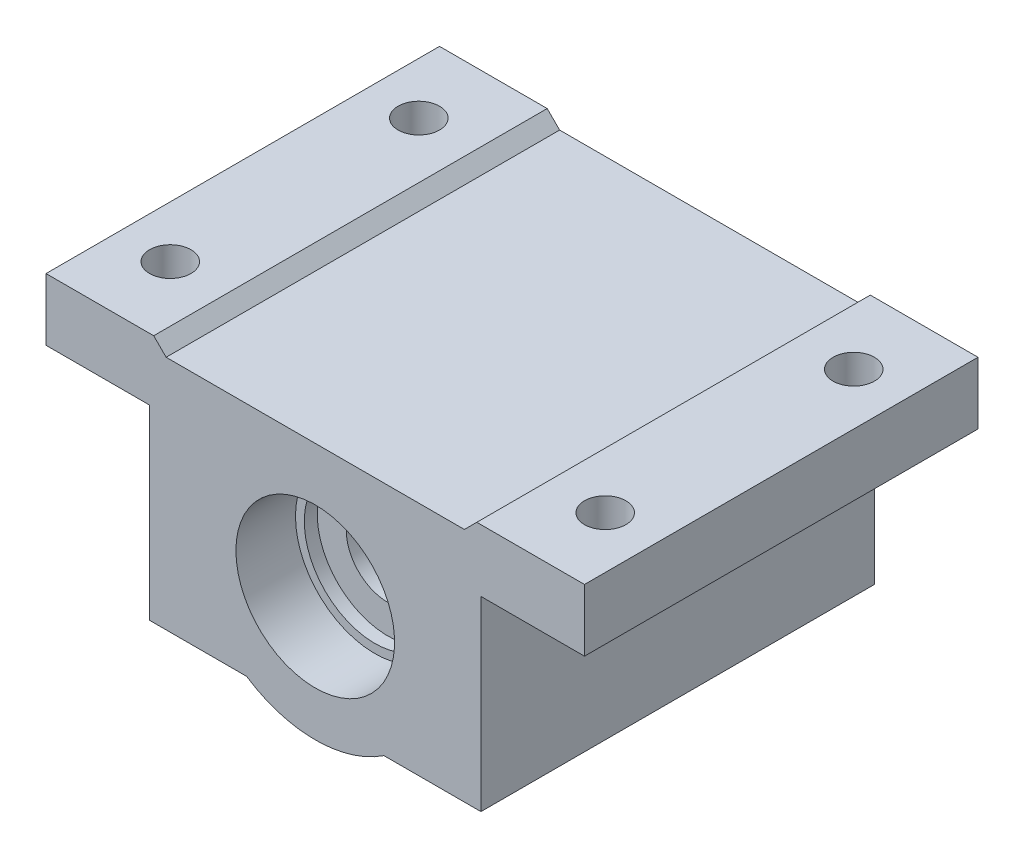
SolidWorks part; units mm, degrees
note: The reader was unsure of these and kept them because the rebuilt part matched: shared geometry of "Grooves<2>".
other "Pillow Block" parameters "D1"=31.4478, "For Shaft Dia"=6.35, "D2"=12.6007, "Supplier Grv Dia P"=13.5128, "Ht G"=11.1125, "Flange Thick H"=4.7625, "Overall Wd D"=41.275, "Overall Ht F"=20.6375, "Supplier Wd G"=25.4, "D3"=16.7204, "D4"=1.4178, "D5"=41.275, "D6"=12.2773, "D7"=50.8, "Supplier Body Height K"=19.05, "Overall Lg B"=30.1625, "Supplier Overall Wd S"=119.0625, "Outside to Outside Grooves"=228.6, "Supplier Grv Wd O"=0.9906, "Dia L"=3.175, "Mounting Holes Center-to-Center J"=33.3375, "Mounting Holes Center-to-Center K"=19.05, "Supplier F"=19.05
material "6063-O, Extruded Rod (SS)"
ref_plane "Front" through (0, 0, 0) normal (0, 0, 1) x (1, 0, 0)
ref_plane "Top" through (0, 0, 0) normal (0, 1, 0) x (1, 0, 0)
ref_plane "Right" through (0, 0, 0) normal (1, 0, 0) x (0, 0, -1)
sketch "Sketch1" plane through (0, 0, 0) normal (0, 0, 1) x (1, 0, 0)
  line L0 (-12.7, -9.525) -> (-12.7, 6.35) construction
  line L1 (-12.7, -9.525) -> (12.7, -9.525) construction
  line L2 (-12.7, 6.35) -> (-20.6375, 6.35)
  line L3 (-20.6375, 11.1125) -> (20.6375, 11.1125) construction
  line L4 (-20.6375, 6.35) -> (-20.6375, 11.1125)
  line L5 (12.7, -9.525) -> (12.7, 6.35) construction
  line L6 (12.7, 6.35) -> (20.6375, 6.35)
  line L7 (20.6375, 6.35) -> (20.6375, 11.1125)
  line L8 (0, 11.1125) -> (0, -9.525) construction
  line L9 (5.2651, -7.9375) -> (12.7, -7.9375)
  line L10 (-12.7, 6.35) -> (-12.7, -7.9375)
  line L11 (-12.7, -7.9375) -> (-5.2651, -7.9375)
  line L12 (12.7, -7.9375) -> (12.7, 6.35)
  line L13 (-12.3825, 11.1125) -> (12.3825, 11.1125) construction
  line L14 (-12.3825, 11.1125) -> (-11.43, 10.16)
  line L15 (-11.43, 10.16) -> (11.43, 10.16)
  line L16 (11.43, 10.16) -> (12.3825, 11.1125)
  line L17 (-12.3825, 11.1125) -> (-20.6375, 11.1125)
  line L18 (12.3825, 11.1125) -> (20.6375, 11.1125)
  circle A0 centre (0, 0) radius 3.175 construction
  circle A1 centre (0, 0) radius 6.0808
  circle A2 centre (0, 0) radius 9.525 construction
  arc A3 (-5.2651, -7.9375) -> (5.2651, -7.9375) centre (0, 0) ccw
  circle A4 centre (0, 0) radius 6.7564 construction
  dimension "D2" = 12.1615
  dimension "D4" = 45
  dimension "D3" = 45
  dimension "D6" = 8.255
  dimension "D1" = 0.9525
extrude "Main Body" add sketch "Sketch1" along normal mid plane 30.1625
sketch "Sketch3" plane through (0, 11.1125, 0) normal (0, 1, 0) x (1, 0, 0)
  line L1 (-16.6687, -9.525) -> (16.6687, -9.525) construction
  line L2 (-16.6687, -9.525) -> (-16.6687, 9.525) construction
  line L3 (-16.6687, 9.525) -> (16.6687, 9.525) construction
  line L4 (16.6687, -9.525) -> (16.6687, 9.525) construction
  line L5 (-12.3825, 15.0813) -> (-20.6375, 15.0813) construction
  line L6 (-16.6687, 9.525) -> (16.6687, -9.525) construction
  line L7 (-16.6687, 9.525) -> (-16.6687, -9.525) construction
  circle A0 centre (-16.6687, 9.525) radius 1.5875
  circle A1 centre (16.6687, 9.525) radius 1.5875
  circle A2 centre (16.6687, -9.525) radius 1.5875
  circle A3 centre (-16.6687, -9.525) radius 1.5875
  point P5 (0, 0)
  dimension "D1" = 5.5562
extrude "Mounting Holes" cut sketch "Sketch3" against normal up to surface (4.7625 mm away) up to face at (16.6688, 6.35, 0)
ref_plane "Plane1" through (0, 0, 0) normal (0, 0, 1) x (1, 0, 0)
sketch "Sketch8" plane through (0, 0, 0) normal (0, 0, 1) x (1, 0, 0)
  circle A0 centre (0, 0) radius 6.0808 construction
  circle A1 centre (0, 0) radius 6.0808
  circle A2 centre (0, 0) radius 3.175 construction
  circle A3 centre (0, 0) radius 3.175
extrude "Interior" add sketch "Sketch8" along normal mid plane 19.05 separate body
sketch "Grooves" plane through (0, 0, 0) normal (1, 0, 0) x (0, 0, -1)
  line L1 (9.525, -6.7564) -> (9.525, 6.7564) construction
  line L2 (9.525, -3.175) -> (9.525, 3.175) construction
  line L4 (-9.525, 3.175) -> (-9.525, -3.175) construction
  line L5 (9.525, -5.4051) -> (9.525, -6.7564)
  line L6 (9.525, -6.7564) -> (10.5156, -6.7564)
  line L7 (10.5156, -5.4051) -> (10.5156, -6.7564)
  line L9 (-9.525, -5.4051) -> (-9.525, -6.7564)
  line L10 (-9.525, -6.7564) -> (-10.5156, -6.7564)
  line L11 (-10.5156, -5.4051) -> (-10.5156, -6.7564)
  line L13 (-10.5156, -5.4051) -> (-9.525, -5.4051)
  line L14 (9.525, -5.4051) -> (10.5156, -5.4051)
  line L15 (9.525, -5.4051) -> (9.525, 5.4051) construction
  point P13 (9.525, 0)
  dimension "Supplier Grv Dia P" = 13.5128
  dimension "D1" = 10.8102
revolve "Grooves " cut sketch "Grooves" angle 360 mid plane about axis through (0, 0, 9.525) along (0, 0, -1)
revolve "Retaining Ring" add sketch "Grooves<2>" angle 360 mid plane about axis through (0, 0, 9.525) along (0, 0, -1)
sketch "Grooves<2>" plane through (0, 0, 0) normal (1, 0, 0) x (0, 0, -1) same geometry as "Grooves"
sketch "Open Retaining Ring" [suppressed] plane through (0, 0, 0) normal (0, 0, 1) x (1, 0, 0)
  line L0 (0, 0) -> (-42.7798, -49.2125)
  line L1 (-42.7798, -49.2125) -> (42.7798, -49.2125)
  line L2 (42.7798, -49.2125) -> (0, 0)
  arc A0 (-31.149, -38.1) -> (31.149, -38.1) centre (0, 0) ccw construction
  dimension "D1" = 82
extrude "Open Retaining Ring " [suppressed] cut sketch "Open Retaining Ring" against normal mid plane 30.1625
sketch "Jog" [suppressed] plane through (0, 0, 0) normal (0, 0, 1) x (1, 0, 0)
  line L0 (57.15, -38.1) -> (-61.9125, -38.1) construction
  line L1 (-57.15, -38.1) -> (-61.9125, -38.1)
  line L2 (-61.9125, -38.1) -> (-61.9125, -19.685)
  line L3 (-61.9125, -19.685) -> (-57.15, -14.9225)
  line L4 (-57.15, 38.1) -> (-57.15, -38.1) construction
  line L5 (-57.15, -14.9225) -> (-57.15, -38.1)
  dimension "D1" = 45
  dimension "D2" = 3.81
extrude "Jog " [suppressed] add sketch "Jog" along normal mid plane 30.1625
sketch "Slot Opening" [suppressed] plane through (0, 0, 0) normal (0, 0, 1) x (1, 0, 0)
  line L0 (0, 0) -> (0, -21.997) construction
  line L1 (-12.7, -21.997) -> (12.7, -21.997)
  line L2 (-12.7, -21.997) -> (-21.997, -38.1)
  line L3 (12.7, -21.997) -> (21.997, -38.1)
  line L4 (21.997, -38.1) -> (31.149, -38.1)
  line L5 (-31.149, -38.1) -> (-21.997, -38.1)
  line L6 (31.149, -38.1) -> (31.149, -49.2125)
  line L7 (31.149, -49.2125) -> (-31.149, -49.2125)
  line L8 (-31.149, -49.2125) -> (-31.149, -38.1)
  line L9 (-57.15, -49.2125) -> (57.15, -49.2125) construction
  circle A0 centre (0, 0) radius 25.4 construction
  dimension "D1" = 60
  dimension "Wd E" = 25.4
extrude "Slot Opening " [suppressed] cut sketch "Slot Opening" against normal through all and the other way through all
mirror "Twin Holes Mirror" [suppressed] about plane through (0, 0, 0) normal (0, 0, 1)
mirror "Twin Bodies" [suppressed] about plane through (0, 0, 0) normal (0, 0, 1)
mirror "Twin Grooves" [suppressed] about plane through (0, 0, 0) normal (0, 0, 1)
equation "\"D6@Sketch1\" = \"Overall Wd D@Sketch1\"  * .2"
equation "\"D1@Sketch1\" = \"Flange Thick H@Sketch1\" * .2"
equation "\"D1@Jog \" = \"Overall Lg B@Main Body\""
equation "\"D2@Jog\" = \"Supplier Body Height K@Sketch1\" * .2"
equation "\"Supplier Grv Dia P@Grooves\" = \"Supplier Grv Dia P@Sketch1\""
equation "\"D2@Sketch1\" = \"Supplier Grv Dia P@Sketch1\" * .9"
equation "\"D1@Grooves\" = \"Supplier Grv Dia P@Sketch1\" * .8"
equation "\"D1@Sketch3\" =  ( \"Overall Lg B@Main Body\" - \"Supplier F@Sketch3\" )  * .5"
equation "\"D1@Open Retaining Ring \" = \"Overall Lg B@Main Body\""
